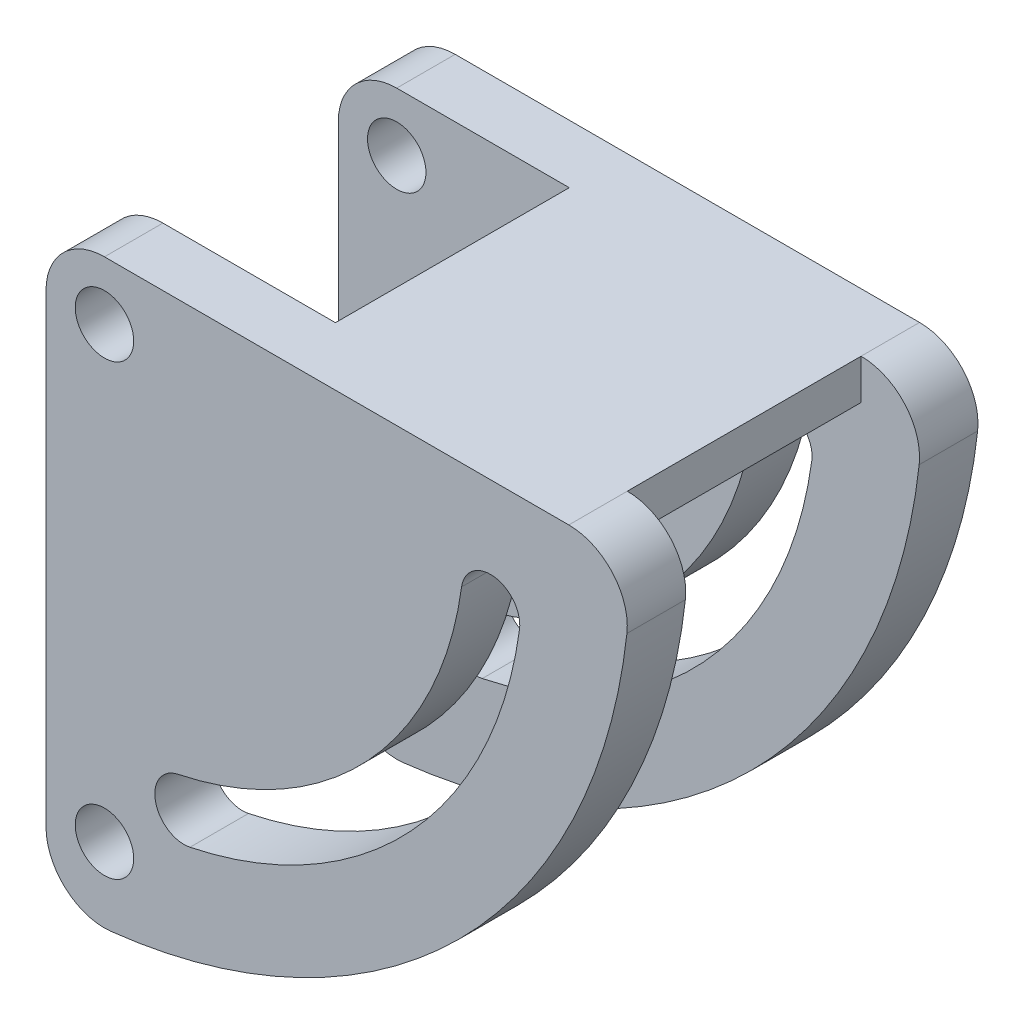
SolidWorks part; units mm, degrees
ref_plane "Front Plane" through (0, 0, 0) normal (0, 0, 1) x (1, 0, 0)
ref_plane "Top Plane" through (0, 0, 0) normal (0, 1, 0) x (1, 0, 0)
ref_plane "Right Plane" through (0, 0, 0) normal (1, 0, 0) x (0, 0, -1)
sketch "Sketch1" plane through (0, 0, 0) normal (0, 0, 1) x (1, 0, 0)
  line L0 (0, 0) -> (30, 0)
  line L1 (0, 0) -> (0, -30)
  arc A0 (0, -30) -> (30, 0) centre (0, 0) ccw
  circle A1 centre (3, -26) radius 1.5
  arc A4 (22.8157, -5.7086) -> (7.0842, -22.5785) centre (3, -3) cw construction
  circle A7 centre (3, -3) radius 1.5
  arc A8 (21.3296, -5.5055) -> (6.7779, -21.1102) centre (3, -3) cw
  arc A9 (7.3905, -24.0469) -> (24.3019, -5.9118) centre (3, -3) ccw
  arc A10 (24.3019, -5.9118) -> (21.3296, -5.5055) centre (22.8157, -5.7086) ccw
  arc A11 (6.7779, -21.1102) -> (7.3905, -24.0469) centre (7.0842, -22.5785) ccw
  point P13 (0, 0)
  dimension "D2" = 3
  dimension "D3" = 3
  dimension "D8" = 30
  dimension "D1" = 20
  dimension "D4" = 3
  dimension "D5" = 3
  dimension "D6" = 4
  dimension "D7" = 3
extrude "Boss-Extrude1" add sketch "Sketch1" along normal blind 3
pattern_linear "LPattern1" count 2 spacing 15 along (0, 0, 1) of "Boss-Extrude1"
fillet "Fillet2" radius 3 3 edges at (0, -30, 1.5) (0, 0, 1.5) (30, 0, 1.5)
fillet "Fillet3" radius 3 3 edges at (0, -30, 16.5) (0, 0, 16.5) (30, 0, 16.5)
sketch "Sketch2" plane through (0, 0, 3) normal (0, 0, 1) x (1, 0, 0)
  line L0 (26.8328, 0) -> (3, 0) construction
  line L1 (11.8553, 0) -> (26.8328, 0)
  line L2 (11.8553, 0) -> (11.8553, -2.0588)
  line L3 (11.8553, -2.0588) -> (26.8328, -2.0588)
  line L4 (26.8328, 0) -> (26.8328, -2.0588)
extrude "Boss-Extrude2" add sketch "Sketch2" along normal up to next
